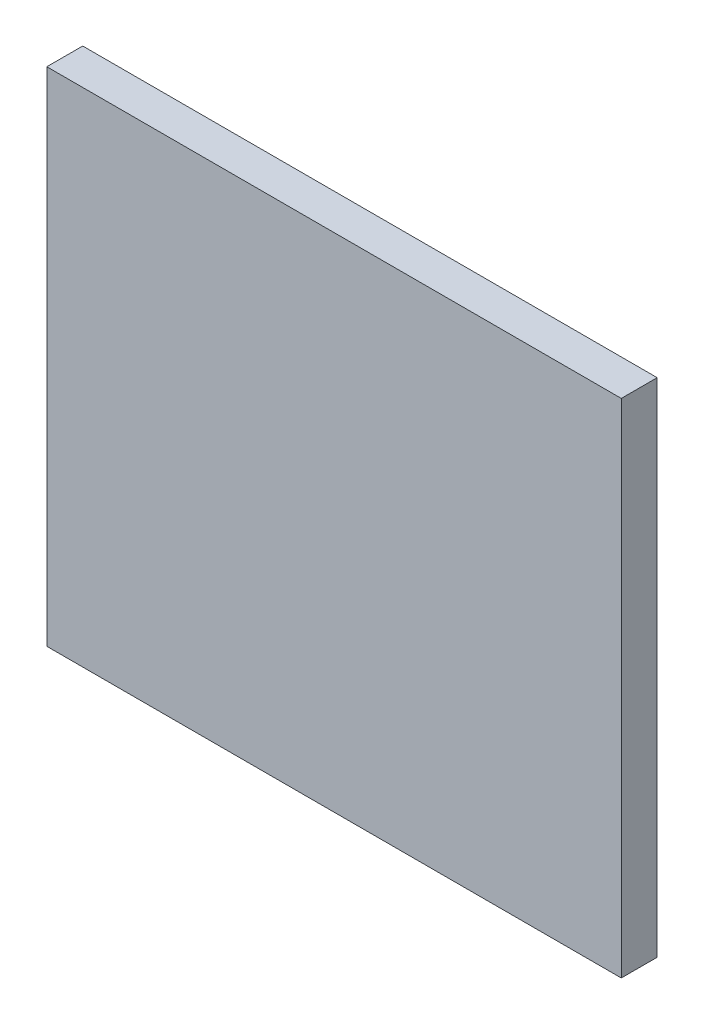
SolidWorks part; units mm, degrees
material "ABS PC"
ref_plane "X-Y Datum" through (0, 0, 0) normal (0, 0, 1) x (1, 0, 0)
ref_plane "X-Z Datum" through (0, 0, 0) normal (0, 1, 0) x (1, 0, 0)
ref_plane "Y-Z Datum" through (0, 0, 0) normal (1, 0, 0) x (0, 0, -1)
sketch "Sketch1" plane through (0, 0, 0) normal (0, 0, 1) x (1, 0, 0)
  line L1 (-50.8, -44.3878) -> (50.8, -44.3878)
  line L2 (-50.8, -44.3878) -> (-50.8, 44.3878)
  line L3 (-50.8, 44.3878) -> (50.8, 44.3878)
  line L4 (50.8, -44.3878) -> (50.8, 44.3878)
  line L5 (-50.8, -44.3878) -> (50.8, 44.3878) construction
  line L6 (-50.8, 44.3878) -> (50.8, -44.3878) construction
  point P0 (0, 0)
  dimension "D1" = 88.7755
  dimension "D2" = 101.6
extrude "Boss-Extrude1" add sketch "Sketch1" along normal blind 6.35
